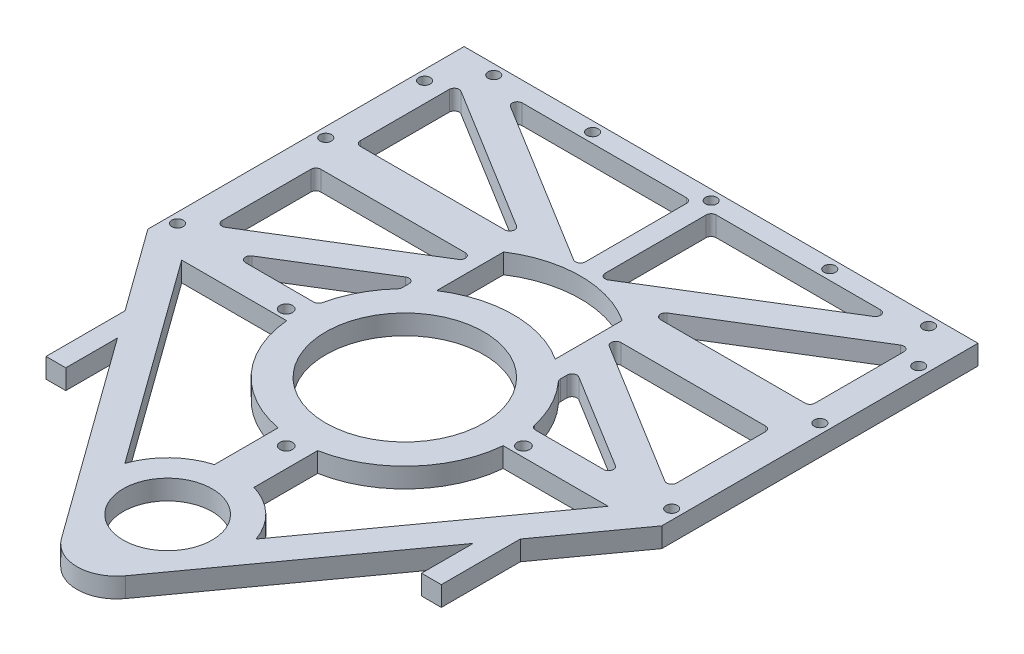
SolidWorks part; units mm, degrees
material "PE High Density"
ref_plane "Front Plane" through (0, 0, 0) normal (0, 0, 1) x (1, 0, 0)
ref_plane "Top Plane" through (0, 0, 0) normal (0, 1, 0) x (1, 0, 0)
ref_plane "Right Plane" through (0, 0, 0) normal (1, 0, 0) x (0, 0, -1)
sketch "Sketch1" plane through (0, 0, 0) normal (0, 1, 0) x (1, 0, 0)
  line L0 (-82.55, -50.8) -> (-10.2956, -150.8445)
  line L2 (-82.55, -50.8) -> (-82.55, 50.8)
  line L3 (-82.55, 50.8) -> (82.55, 50.8)
  line L4 (82.55, -50.8) -> (82.55, 50.8)
  line L5 (-82.55, -50.8) -> (82.55, 50.8) construction
  line L6 (-82.55, 50.8) -> (82.55, -50.8) construction
  line L7 (10.2956, -150.8445) -> (82.55, -50.8)
  line L8 (0, 50.8) -> (0, -165.1) construction
  arc A0 (-10.2956, -150.8445) -> (10.2956, -150.8445) centre (0, -143.4088) ccw
  point P0 (0, 0)
  dimension "D3" = 12.7
  dimension "D1" = 165.1
  dimension "D2" = 101.6
  dimension "D4" = 215.9
extrude "Boss-Extrude1" add sketch "Sketch1" along normal blind 6.35
sketch "Sketch4" plane through (0, 6.35, 0) normal (0, 1, 0) x (1, 0, 0)
  line L0 (-63.5, -77.1769) -> (-63.5, -102.5769)
  line L1 (-82.55, -50.8) -> (-10.2956, -150.8445) construction
  line L2 (0, -156.1088) -> (0, 50.8) construction
  line L3 (82.55, 50.8) -> (-82.55, 50.8) construction
  line L4 (-63.5, -77.1769) -> (-57.15, -85.9692)
  line L5 (-57.15, -85.9692) -> (-57.15, -102.5769)
  line L6 (-57.15, -102.5769) -> (-63.5, -102.5769)
  line L7 (57.15, -102.5769) -> (63.5, -102.5769)
  line L8 (57.15, -85.9692) -> (57.15, -102.5769)
  line L9 (63.5, -77.1769) -> (57.15, -85.9692)
  line L10 (63.5, -77.1769) -> (63.5, -102.5769)
  arc A0 (-10.2956, -150.8445) -> (10.2956, -150.8445) centre (0, -143.4088) ccw construction
  dimension "D1" = 6.35
  dimension "D2" = 25.4
  dimension "D3" = 127
extrude "Boss-Extrude2" add sketch "Sketch4" against normal up to surface (6.35 mm away) up to face at (0, 0, 51.1589)
sketch "Sketch2" plane through (0, 6.35, 0) normal (0, 1, 0) x (1, 0, 0)
  line L0 (-82.55, 0) -> (82.55, 0) construction
  line L1 (-82.55, 50.8) -> (-82.55, -50.8) construction
  line L2 (82.55, -50.8) -> (82.55, 50.8) construction
  line L3 (0, 0) -> (-82.55, 50.8) construction
  line L4 (82.55, 50.8) -> (-82.55, 50.8) construction
  line L5 (0, 50.8) -> (0, -156.1088) construction
  line L6 (-44.1877, 38.1) -> (-7.9375, 38.1)
  line L7 (-6.35, 36.5125) -> (-6.35, 14.2047)
  line L8 (-8.7695, 12.8527) -> (-45.0197, 35.1605)
  line L9 (-69.85, 32.6876) -> (-69.85, 7.9375)
  line L10 (-68.2625, 6.35) -> (-28.0435, 6.35)
  line L11 (-27.2115, 9.2895) -> (-67.4305, 34.0396)
  line L30 (-82.55, -50.8) -> (82.55, -50.8) construction
  line L31 (-54.2707, -62.842) -> (-18.914, -111.7974)
  line L36 (10.2956, -150.8445) -> (57.15, -85.9692) construction
  line L44 (27.2115, 9.2895) -> (67.4305, 34.0396)
  line L45 (68.2625, 6.35) -> (28.0435, 6.35)
  line L46 (69.85, 32.6876) -> (69.85, 7.9375)
  line L47 (6.35, 36.5125) -> (6.35, 14.2047)
  line L48 (8.7695, 12.8527) -> (45.0197, 35.1605)
  line L49 (44.1877, 38.1) -> (7.9375, 38.1)
  line L50 (-27.2115, -9.2895) -> (-67.4305, -34.0396)
  line L51 (-68.2625, -6.35) -> (-28.0435, -6.35)
  line L52 (-69.85, -32.6876) -> (-69.85, -7.9375)
  line L59 (69.85, -32.6876) -> (69.85, -7.9375)
  line L60 (68.2625, -6.35) -> (28.0435, -6.35)
  line L61 (27.2115, -9.2895) -> (67.4305, -34.0396)
  line L62 (-9.525, -105.8465) -> (-9.525, -78.8408)
  line L64 (-28.0408, -60.325) -> (-52.9837, -60.325)
  line L65 (-57.15, -85.9692) -> (-10.2956, -150.8445) construction
  line L66 (28.0408, -60.325) -> (52.9837, -60.325)
  line L67 (9.525, -105.8465) -> (9.525, -78.8408)
  line L68 (54.2707, -62.842) -> (18.914, -111.7974)
  line L69 (-54.5065, -44.45) -> (-29.0994, -44.45)
  line L71 (-6.35, -21.7006) -> (-6.35, -14.2047)
  line L72 (-8.7695, -12.8527) -> (-55.3385, -41.5105)
  line L73 (6.35, -21.7006) -> (6.35, -14.2047)
  line L74 (54.5065, -44.45) -> (29.0994, -44.45)
  line L75 (8.7695, -12.8527) -> (55.3385, -41.5105)
  arc A0 (-10.2956, -150.8445) -> (10.2956, -150.8445) centre (0, -143.4088) ccw construction
  circle A1 centre (0, -127) radius 14.2875
  circle A2 centre (0, -127) radius 22.3072 construction
  arc A5 (-6.35, 14.2047) -> (-8.7695, 12.8527) centre (-7.9375, 14.2047) cw
  arc A6 (-7.9375, 38.1) -> (-6.35, 36.5125) centre (-7.9375, 36.5125) cw
  arc A7 (-44.1877, 38.1) -> (-45.0197, 35.1605) centre (-44.1877, 36.5125) ccw
  arc A8 (-28.0435, 6.35) -> (-27.2115, 9.2895) centre (-28.0435, 7.9375) ccw
  arc A9 (-69.85, 7.9375) -> (-68.2625, 6.35) centre (-68.2625, 7.9375) ccw
  arc A10 (-69.85, 32.6876) -> (-67.4305, 34.0396) centre (-68.2625, 32.6876) cw
  arc A11 (28.0435, 6.35) -> (27.2115, 9.2895) centre (28.0435, 7.9375) cw
  arc A12 (69.85, 7.9375) -> (68.2625, 6.35) centre (68.2625, 7.9375) cw
  arc A13 (69.85, 32.6876) -> (67.4305, 34.0396) centre (68.2625, 32.6876) ccw
  arc A14 (7.9375, 38.1) -> (6.35, 36.5125) centre (7.9375, 36.5125) ccw
  arc A15 (6.35, 14.2047) -> (8.7695, 12.8527) centre (7.9375, 14.2047) ccw
  arc A16 (44.1877, 38.1) -> (45.0197, 35.1605) centre (44.1877, 36.5125) cw
  arc A17 (-69.85, -7.9375) -> (-68.2625, -6.35) centre (-68.2625, -7.9375) cw
  arc A18 (-69.85, -32.6876) -> (-67.4305, -34.0396) centre (-68.2625, -32.6876) ccw
  arc A19 (-28.0435, -6.35) -> (-27.2115, -9.2895) centre (-28.0435, -7.9375) cw
  arc A26 (69.85, -32.6876) -> (67.4305, -34.0396) centre (68.2625, -32.6876) cw
  arc A27 (69.85, -7.9375) -> (68.2625, -6.35) centre (68.2625, -7.9375) ccw
  arc A28 (28.0435, -6.35) -> (27.2115, -9.2895) centre (28.0435, -7.9375) ccw
  circle A37 centre (0, -50.8) radius 19.05
  circle A38 centre (0, -50.8) radius 28.575 construction
  arc A39 (-16.4559, -111.9397) -> (-10.3742, -107.2519) centre (0, -127) cw
  arc A40 (-26.565, -61.3276) -> (-10.5276, -77.365) centre (0, -50.8) ccw
  arc A41 (-16.4559, -111.9397) -> (-18.914, -111.7974) centre (-17.627, -110.8679) cw
  arc A42 (-10.3742, -107.2519) -> (-9.525, -105.8465) centre (-11.1125, -105.8465) ccw
  arc A43 (-9.525, -78.8408) -> (-10.5276, -77.365) centre (-11.1125, -78.8408) ccw
  arc A44 (-26.565, -61.3276) -> (-28.0408, -60.325) centre (-28.0408, -61.9125) ccw
  arc A45 (-54.2707, -62.842) -> (-52.9837, -60.325) centre (-52.9837, -61.9125) cw
  arc A46 (54.2707, -62.842) -> (52.9837, -60.325) centre (52.9837, -61.9125) ccw
  arc A47 (26.565, -61.3276) -> (28.0408, -60.325) centre (28.0408, -61.9125) cw
  arc A48 (9.525, -78.8408) -> (10.5276, -77.365) centre (11.1125, -78.8408) cw
  arc A49 (10.3742, -107.2519) -> (9.525, -105.8465) centre (11.1125, -105.8465) cw
  arc A50 (16.4559, -111.9397) -> (18.914, -111.7974) centre (17.627, -110.8679) ccw
  arc A51 (26.565, -61.3276) -> (10.5276, -77.365) centre (0, -50.8) cw
  arc A52 (16.4559, -111.9397) -> (10.3742, -107.2519) centre (0, -127) ccw
  arc A53 (-7.5197, -23.2322) -> (-27.5678, -43.2803) centre (0, -50.8) ccw
  arc A54 (-54.5065, -44.45) -> (-55.3385, -41.5105) centre (-54.5065, -42.8625) cw
  arc A55 (-29.0994, -44.45) -> (-27.5678, -43.2803) centre (-29.0994, -42.8625) ccw
  arc A56 (-7.5197, -23.2322) -> (-6.35, -21.7006) centre (-7.9375, -21.7006) ccw
  arc A57 (-6.35, -14.2047) -> (-8.7695, -12.8527) centre (-7.9375, -14.2047) ccw
  arc A58 (6.35, -14.2047) -> (8.7695, -12.8527) centre (7.9375, -14.2047) cw
  arc A59 (7.5197, -23.2322) -> (27.5678, -43.2803) centre (0, -50.8) cw
  arc A60 (29.0994, -44.45) -> (27.5678, -43.2803) centre (29.0994, -42.8625) cw
  arc A61 (54.5065, -44.45) -> (55.3385, -41.5105) centre (54.5065, -42.8625) ccw
  arc A62 (7.5197, -23.2322) -> (6.35, -21.7006) centre (7.9375, -21.7006) cw
  point P63 (-6.35, 11.3637)
  point P65 (-6.35, 38.1)
  point P68 (-49.7964, 38.1)
  point P71 (-22.4348, 6.35)
  point P74 (-69.85, 6.35)
  point P77 (-69.85, 35.5286)
  point P78 (0, -50.8)
  point P93 (-17.7204, -113.4501)
  point P97 (-9.525, -77.7408)
  point P100 (-26.9408, -60.325)
  point P128 (9.525, -77.7408)
  point P137 (-27.8605, -44.45)
  point P140 (-6.35, -22.9395)
  point P147 (6.35, -22.9395)
  dimension "D7" = 28.575
  dimension "D12" = 1.5875
  dimension "D13" = 15.875
  dimension "D10" = 38.1
  dimension "D11" = 57.15
  dimension "D14" = 9.525
  dimension "D16" = 1.5875
  dimension "D17" = 6.35
  dimension "D20" = 1.5875
  dimension "D1" = 12.7
  dimension "D2" = 6.35
  dimension "D3" = 6.35
  dimension "D4" = 12.7
  dimension "D5" = 6.35
  dimension "D6" = 6.35
  dimension "D8" = 76.2
  dimension "D15" = 9.525
  dimension "D18" = 12.7
  dimension "D19" = 6.35
extrude "Cut-Extrude1" [suppressed] cut sketch "Sketch2" against normal up to next contours A19 L51 A17 L52 A18 L50 | A10 L9 A9 L10 A8 L11 | L6 A7 L8 A5 L7 A6 | A16 L49 A14 L47 A15 L48 | L46 A13 L44 A11 L45 A12 | L60 A28 L61 A26 L59 A27 | A1 | L71 A57 L72 A54 L69 A55 A53 A56 | A37 | A62 A59 A60 L74 A61 L75 A58 L73 | A52 A50 L68 A46 L66 A47 A51 A48 L67 A49 | A45 L31 A41 A39 A42 L62 A43 A40 A44 L64
sketch "Sketch3" plane through (0, 6.35, 0) normal (0, 1, 0) x (1, 0, 0)
  line L0 (-82.55, 0) -> (82.55, 0) construction
  line L1 (-82.55, 50.8) -> (-82.55, -50.8) construction
  line L2 (82.55, -50.8) -> (82.55, 50.8) construction
  line L3 (-82.55, 50.8) -> (0, 0) construction
  line L4 (82.55, 50.8) -> (-82.55, 50.8) construction
  line L5 (0, 50.8) -> (0, 0) construction
  line L6 (-58.3675, 41.5105) -> (-5.5945, 9.0348)
  line L7 (-3.175, 10.3868) -> (-3.175, 42.8625)
  line L8 (-4.7625, 44.45) -> (-57.5355, 44.45)
  line L9 (-73.025, 36.5055) -> (-73.025, 7.9375)
  line L10 (-71.4375, 6.35) -> (-25.0145, 6.35)
  line L11 (-24.1825, 9.2895) -> (-70.6055, 37.8575)
  line L12 (4.7625, 44.45) -> (57.5355, 44.45)
  line L13 (3.175, 10.3868) -> (3.175, 42.8625)
  line L14 (58.3675, 41.5105) -> (5.5945, 9.0348)
  line L15 (24.1825, 9.2895) -> (70.6055, 37.8575)
  line L16 (71.4375, 6.35) -> (25.0145, 6.35)
  line L17 (73.025, 36.5055) -> (73.025, 7.9375)
  line L18 (73.025, -36.5055) -> (73.025, -7.9375)
  line L19 (71.4375, -6.35) -> (25.0145, -6.35)
  line L20 (24.1825, -9.2895) -> (70.6055, -37.8575)
  line L21 (-24.1825, -9.2895) -> (-70.6055, -37.8575)
  line L22 (-71.4375, -6.35) -> (-25.0145, -6.35)
  line L23 (-73.025, -36.5055) -> (-73.025, -7.9375)
  line L24 (-82.55, -50.8) -> (82.55, -50.8) construction
  line L25 (0, 0) -> (-82.55, -50.8) construction
  line L30 (0, -50.8) -> (0, -127) construction
  line L31 (-6.35, -85.1429) -> (-6.35, -105.6157)
  line L32 (-68.5075, -53.975) -> (-34.7804, -53.975)
  line L33 (-68.5075, -53.975) -> (-21.0661, -119.6631)
  line L34 (-82.55, -50.8) -> (-63.5, -77.1769) construction
  line L35 (6.35, -85.1429) -> (6.35, -105.6157)
  line L36 (68.5075, -53.975) -> (21.0661, -119.6631)
  line L37 (68.5075, -53.975) -> (34.7804, -53.975)
  line L38 (-19.05, -21.5279) -> (-19.05, 0)
  line L39 (19.05, -21.5279) -> (19.05, 0)
  line L40 (-82.55, -50.8) -> (-63.5, -77.1769) construction
  line L41 (-57.5355, -44.45) -> (-35.6393, -44.45)
  line L42 (-58.3675, -41.5105) -> (-27.8195, -22.7117)
  line L43 (-25.4, -24.0637) -> (-25.4, -26.2066)
  line L44 (25.4, -24.0637) -> (25.4, -26.2066)
  line L45 (57.5355, -44.45) -> (35.6393, -44.45)
  line L46 (58.3675, -41.5105) -> (27.8195, -22.7117)
  arc A0 (-5.5945, 9.0348) -> (-3.175, 10.3868) centre (-4.7625, 10.3868) ccw
  arc A1 (-3.175, 42.8625) -> (-4.7625, 44.45) centre (-4.7625, 42.8625) ccw
  arc A2 (-58.3675, 41.5105) -> (-57.5355, 44.45) centre (-57.5355, 42.8625) cw
  arc A3 (-25.0145, 6.35) -> (-24.1825, 9.2895) centre (-25.0145, 7.9375) ccw
  arc A4 (-73.025, 7.9375) -> (-71.4375, 6.35) centre (-71.4375, 7.9375) ccw
  arc A5 (-73.025, 36.5055) -> (-70.6055, 37.8575) centre (-71.4375, 36.5055) cw
  arc A6 (3.175, 42.8625) -> (4.7625, 44.45) centre (4.7625, 42.8625) cw
  arc A7 (58.3675, 41.5105) -> (57.5355, 44.45) centre (57.5355, 42.8625) ccw
  arc A8 (5.5945, 9.0348) -> (3.175, 10.3868) centre (4.7625, 10.3868) cw
  arc A9 (73.025, 7.9375) -> (71.4375, 6.35) centre (71.4375, 7.9375) cw
  arc A10 (73.025, 36.5055) -> (70.6055, 37.8575) centre (71.4375, 36.5055) ccw
  arc A11 (25.0145, 6.35) -> (24.1825, 9.2895) centre (25.0145, 7.9375) cw
  arc A12 (25.0145, -6.35) -> (24.1825, -9.2895) centre (25.0145, -7.9375) ccw
  arc A13 (73.025, -36.5055) -> (70.6055, -37.8575) centre (71.4375, -36.5055) cw
  arc A14 (73.025, -7.9375) -> (71.4375, -6.35) centre (71.4375, -7.9375) ccw
  arc A15 (-73.025, -36.5055) -> (-70.6055, -37.8575) centre (-71.4375, -36.5055) ccw
  arc A16 (-73.025, -7.9375) -> (-71.4375, -6.35) centre (-71.4375, -7.9375) cw
  arc A17 (-25.0145, -6.35) -> (-24.1825, -9.2895) centre (-25.0145, -7.9375) cw
  circle A18 centre (0, -50.8) radius 25.4
  circle A19 centre (0, -50.8) radius 34.925 construction
  arc A29 (-25.8141, -27.2758) -> (-34.0898, -43.2076) centre (0, -50.8) ccw
  circle A30 centre (0, -127) radius 14.2875 construction
  circle A31 centre (0, -127) radius 14.2875
  circle A32 centre (0, -127) radius 22.3072 construction
  circle A33 centre (0, -127) radius 22.3072 construction
  arc A34 (-34.7804, -53.975) -> (-6.35, -85.1429) centre (0, -50.8) ccw
  arc A35 (-6.35, -105.6157) -> (-21.0661, -119.6631) centre (0, -127) ccw
  arc A36 (6.35, -105.6157) -> (21.0661, -119.6631) centre (0, -127) cw
  arc A37 (34.7804, -53.975) -> (6.35, -85.1429) centre (0, -50.8) cw
  arc A38 (19.05, -21.5279) -> (-19.05, -21.5279) centre (0, -50.8) ccw
  arc A39 (-19.05, 0) -> (19.05, 0) centre (0, -29.2721) cw
  arc A40 (-35.6393, -44.45) -> (-34.0898, -43.2076) centre (-35.6393, -42.8625) ccw
  arc A41 (-25.4, -26.2066) -> (-25.8141, -27.2758) centre (-26.9875, -26.2066) cw
  arc A42 (-27.8195, -22.7117) -> (-25.4, -24.0637) centre (-26.9875, -24.0637) cw
  arc A43 (-57.5355, -44.45) -> (-58.3675, -41.5105) centre (-57.5355, -42.8625) cw
  arc A44 (25.4, -26.2066) -> (25.8141, -27.2758) centre (26.9875, -26.2066) ccw
  arc A45 (27.8195, -22.7117) -> (25.4, -24.0637) centre (26.9875, -24.0637) ccw
  arc A46 (25.8141, -27.2758) -> (34.0898, -43.2076) centre (0, -50.8) cw
  arc A47 (35.6393, -44.45) -> (34.0898, -43.2076) centre (35.6393, -42.8625) cw
  arc A48 (57.5355, -44.45) -> (58.3675, -41.5105) centre (57.5355, -42.8625) ccw
  point P82 (-34.3429, -44.45)
  point P85 (-25.4, -26.8293)
  point P115 (0, -15.875)
  dimension "D7" = 1.5875
  dimension "D8" = 50.8
  dimension "D9" = 9.525
  dimension "D12" = 6.35
  dimension "D13" = 9.525
  dimension "D16" = 38.1
  dimension "D17" = 50.8
  dimension "D18" = 1.5875
  dimension "D1" = 6.35
  dimension "D2" = 3.175
  dimension "D3" = 4.7625
  dimension "D4" = 4.7625
  dimension "D5" = 9.525
  dimension "D6" = 6.35
  dimension "D10" = 6.35
  dimension "D11" = 4.7625
  dimension "D14" = 6.35
  dimension "D15" = 3.175
extrude "Cut-Extrude2" cut sketch "Sketch3" against normal up to next
sketch "Sketch5" plane through (0, 6.35, 0) normal (0, 1, 0) x (1, 0, 0)
  line L9 (79.375, -50.8) -> (79.375, 47.625)
  line L10 (79.375, 47.625) -> (-79.375, 47.625)
  line L11 (-79.375, 47.625) -> (-79.375, -50.8)
  line L12 (79.375, -50.8) -> (79.375, 47.625) construction
  line L13 (79.375, 47.625) -> (-79.375, 47.625) construction
  line L14 (-79.375, 47.625) -> (-79.375, -50.8) construction
  point P0 (-79.375, 3.175)
  point P1 (-79.375, -44.45)
  point P2 (-79.375, 34.925)
  point P3 (79.375, 34.925)
  point P4 (79.375, 3.175)
  point P5 (79.375, -44.45)
  point P6 (38.1, 47.625)
  point P7 (69.85, 47.625)
  point P8 (-69.85, 47.625)
  point P9 (-38.1, 47.625)
  point P12 (0, 47.625)
  dimension "D2" = 12.7
  dimension "D3" = 6.35
  dimension "D4" = 9.525
  dimension "D5" = 9.525
  dimension "D6" = 38.1
  dimension "D7" = 38.1
  dimension "D8" = 31.75
  dimension "D1" = 3.175
hole_wizard "#6 Clearance Hole1" positions "Sketch6" profile "Sketch7" hole size "#6" standard "ANSI Inch" end condition up to next
sketch "Sketch6" plane through (0, 6.35, 0) normal (0, 1, 0) x (1, 0, 0)
  point P3 (-79.375, -44.45)
  point P6 (-79.375, 3.175)
  point P11 (-69.85, 47.625)
  point P14 (-79.375, 34.925)
  point P17 (-38.1, 47.625)
  point P20 (0, 47.625)
  point P23 (38.1, 47.625)
  point P26 (69.85, 47.625)
  point P28 (79.375, 34.925)
  point P31 (79.375, 3.175)
  point P34 (79.375, -44.45)
sketch "Sketch7" plane through (-79.375, 6.35, 44.45) normal (1, 0, 0) x (0, 0, 1)
  line L0 (0, 0) -> (0, 6.35)
  line L1 (0, 6.35) -> (1.8288, 6.35)
  line L2 (1.8288, 6.35) -> (1.8288, 0)
  line L5 (1.8288, 0) -> (0, 0)
  line L11 (0, -6.35) -> (0, 107.95) construction
  dimension "Thru Hole Dia." = 3.6576
  dimension "Thru Hole Depth" = 6.35
sketch "Sketch8" plane through (0, 6.35, 0) normal (0, 1, 0) x (1, 0, 0)
  line L0 (-25.4, -50.8) -> (25.4, -50.8) construction
  line L1 (-38.1, -50.8) -> (38.1, -50.8) construction
  line L2 (0, -50.8) -> (0, -88.9) construction
  circle A0 centre (0, -50.8) radius 25.4 construction
  point P7 (0, -50.8)
  point P8 (0, -50.8)
  dimension "D1" = 76.2
  dimension "D2" = 38.1
hole_wizard "Tap Drill for #10-32 Tap1" positions "Sketch9" profile "Sketch10" hole size "#10-32" standard "ANSI Inch" end condition up to next
sketch "Sketch9" plane through (0, 6.35, 0) normal (0, 1, 0) x (1, 0, 0)
  point P0 (-38.1, -50.8)
  point P3 (0, -88.9)
  point P6 (38.1, -50.8)
sketch "Sketch10" plane through (-38.1, 6.35, 50.8) normal (1, 0, 0) x (0, 0, 1)
  line L0 (0, 0) -> (0, 6.35)
  line L1 (0, 6.35) -> (2.0193, 6.35)
  line L2 (2.0193, 6.35) -> (2.0193, 0)
  line L5 (2.0193, 0) -> (0, 0)
  line L11 (0, -6.35) -> (0, 107.95) construction
  dimension "Thru Hole Dia." = 4.0386
  dimension "Thru Hole Depth" = 6.35
